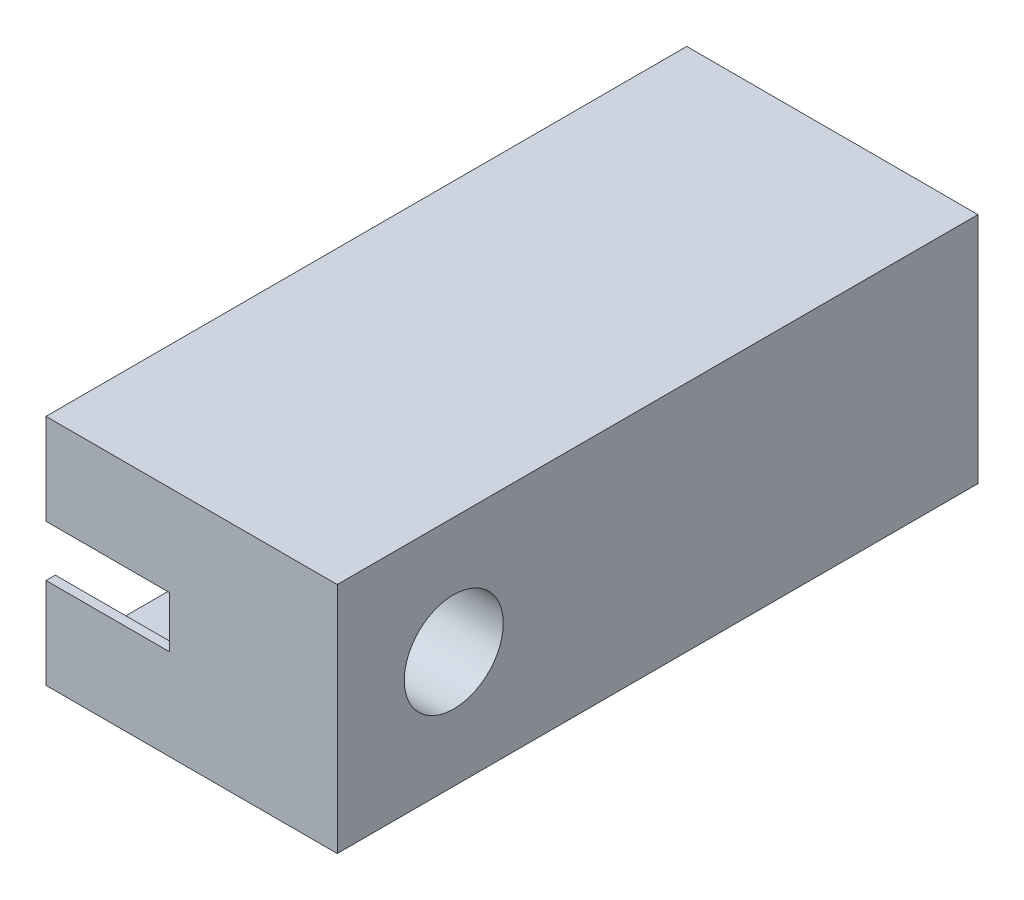
SolidWorks part; units mm, degrees
ref_plane "Front Plane" through (0, 0, 0) normal (0, 0, 1) x (1, 0, 0)
ref_plane "Top Plane" through (0, 0, 0) normal (0, 1, 0) x (1, 0, 0)
ref_plane "Right Plane" through (0, 0, 0) normal (1, 0, 0) x (0, 0, -1)
sketch "Sketch1" plane through (0, 0, 0) normal (1, 0, 0) x (0, 0, -1)
  line L1 (-12.7, 12.7) -> (57.15, 12.7)
  line L2 (-12.7, 12.7) -> (-12.7, -12.7)
  line L3 (-12.7, -12.7) -> (57.15, -12.7)
  line L4 (57.15, 12.7) -> (57.15, -12.7)
  circle A0 centre (0, 0) radius 5.3975
  dimension "D1" = 10.795
  dimension "D2" = 12.7
  dimension "D3" = 57.15
  dimension "D4" = 12.7
  dimension "D5" = 12.7
extrude "Boss-Extrude1" add sketch "Sketch1" along normal blind 31.75
sketch "Sketch2" plane through (0, 0, 0) normal (-1, 0, 0) x (0, 0, 1)
  line L0 (-59.69, 10.4775) -> (11.684, 10.4775)
  line L1 (11.684, 10.4775) -> (11.684, -10.4775)
  line L2 (11.684, -10.4775) -> (-59.69, -10.4775)
  line L3 (-59.69, -10.4775) -> (-59.69, 10.4775)
  line L4 (12.7, 12.7) -> (12.7, -12.7) construction
  line L5 (12.7, 12.7) -> (12.7, -12.7)
  line L6 (-57.15, -12.7) -> (-57.15, 12.7) construction
  line L8 (11.684, 2.794) -> (16.764, 2.794)
  line L9 (11.684, 2.794) -> (11.684, -2.794)
  line L10 (11.684, -2.794) -> (16.764, -2.794)
  line L11 (16.764, 2.794) -> (16.764, -2.794)
  point P6 (12.7, 0)
  point P7 (11.684, 0)
  point P14 (16.764, 0)
  dimension "D1" = 20.955
  dimension "D2" = 1.016
  dimension "D3" = 2.54
  dimension "D4" = 5.588
  dimension "D5" = 5.08
extrude "Cut-Extrude1" cut sketch "Sketch2" against normal blind 22.86 contours L3 L0 L1 L2
extrude "Cut-Extrude2" cut sketch "Sketch2<3>" against normal blind 13.462 contours L11 L10 L9 L8
sketch "Sketch2<3>" plane through (0, 0, 0) normal (-1, 0, 0) x (0, 0, 1) same geometry as "Sketch2"
sketch "Sketch3" plane through (22.86, 0, 0) normal (-1, 0, 0) x (0, 0, 1)
  line L0 (-57.15, -10.4775) -> (-57.15, 10.4775) construction
  line L1 (-57.15, 12.7) -> (12.7, 12.7) construction
  line L2 (12.7, -12.7) -> (-57.15, -12.7) construction
  circle A0 centre (-53.975, 6.35) radius 1.5875
  circle A1 centre (-53.975, -6.35) radius 1.5875
  point P6 (0, 0)
  dimension "D1" = 3.175
  dimension "D2" = 3.175
  dimension "D3" = 6.35
  dimension "D4" = 6.35
extrude "Cut-Extrude3" cut sketch "Sketch3" against normal through all contours A0 | A1
sketch "Sketch8" plane through (31.75, 0, 0) normal (1, 0, 0) x (0, 0, -1)
  circle A0 centre (53.975, -6.35) radius 1.5875 construction
  circle A1 centre (53.975, 6.35) radius 1.5875 construction
  circle A2 centre (53.975, -6.35) radius 1.5875
  circle A3 centre (53.975, 6.35) radius 1.5875
extrude "Boss-Extrude2" add sketch "Sketch8" against normal blind 2.54
equation "\"3DP_Oversize\"= .05"
equation "\"D1@Sketch1\"=\"3DP_Oversize\"+.375"
